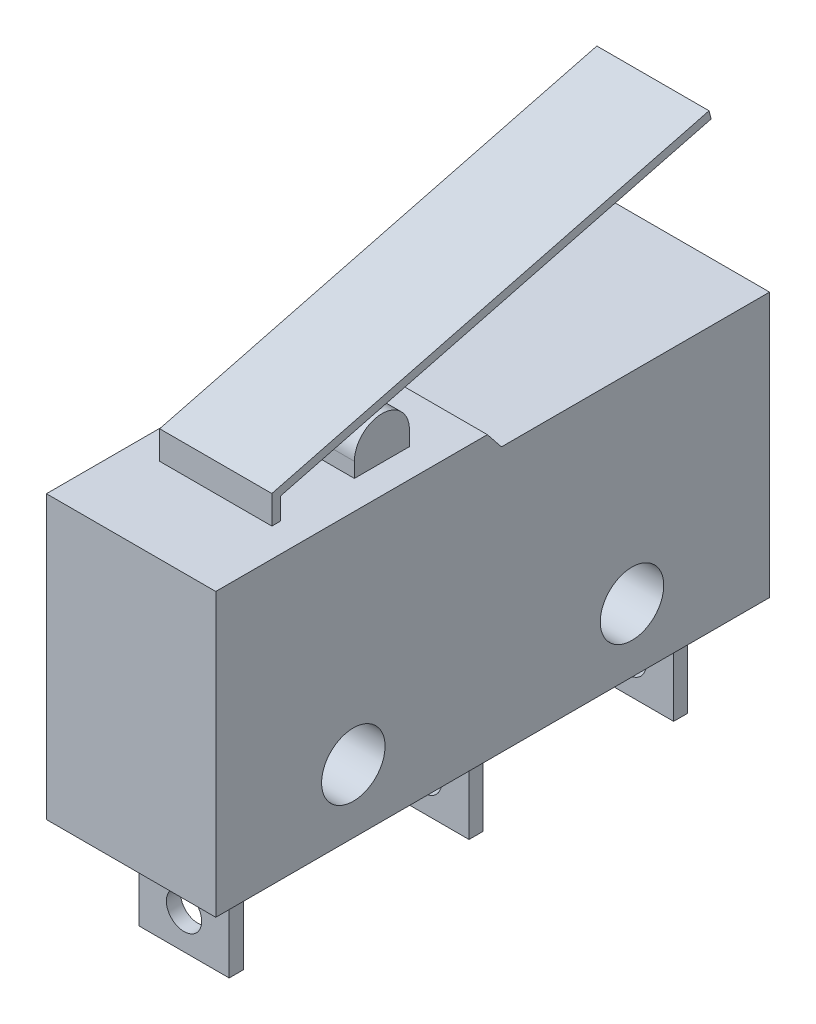
SolidWorks part; units mm, degrees
material "Nylon 101"
ref_plane "Front Plane" through (0, 0, 0) normal (0, 0, 1) x (1, 0, 0)
ref_plane "Top Plane" through (0, 0, 0) normal (0, 1, 0) x (1, 0, 0)
ref_plane "Right Plane" through (0, 0, 0) normal (1, 0, 0) x (0, 0, -1)
sketch "Sketch1" plane through (0, 0, 0) normal (1, 0, 0) x (0, 0, -1)
  line L0 (0, 0) -> (0, 10.16)
  line L1 (0, 10.16) -> (3.048, 10.16)
  line L2 (3.048, 10.16) -> (3.048, 11.176)
  line L3 (3.048, 11.176) -> (18.7878, 15.24)
  line L4 (3.3528, 10.16) -> (3.3528, 10.9399)
  line L5 (3.3528, 10.9399) -> (18.864, 14.9449)
  line L6 (18.7878, 15.24) -> (18.864, 14.9449)
  line L7 (3.3528, 10.16) -> (6.0198, 10.16)
  line L8 (6.0198, 10.16) -> (6.0198, 10.6934)
  line L9 (8.001, 10.6934) -> (8.001, 10.16)
  line L10 (8.001, 10.16) -> (9.779, 10.16)
  line L11 (10.287, 9.525) -> (19.939, 9.525)
  line L12 (9.779, 10.16) -> (10.287, 9.525)
  line L13 (0, 0) -> (1.905, 0)
  line L14 (19.939, 0) -> (19.939, 9.525)
  line L15 (1.905, 0) -> (1.905, -3.556)
  line L16 (1.905, -3.556) -> (2.413, -3.556)
  line L17 (2.413, -3.556) -> (2.413, 0)
  line L24 (2.413, 0) -> (10.541, 0)
  line L25 (11.049, -3.556) -> (11.049, 0)
  line L26 (10.541, 0) -> (10.541, -3.556)
  line L27 (10.541, -3.556) -> (11.049, -3.556)
  line L28 (18.415, -3.556) -> (18.415, 0)
  line L29 (17.907, 0) -> (17.907, -3.556)
  line L30 (17.907, -3.556) -> (18.415, -3.556)
  line L32 (18.415, 0) -> (19.939, 0)
  line L40 (11.049, 0) -> (17.907, 0)
  arc A0 (6.0198, 10.6934) -> (8.001, 10.6934) centre (7.0104, 10.6934) cw
  circle A1 centre (4.953, 2.286) radius 1.143
  circle A2 centre (14.986, 2.286) radius 1.143
  dimension "D5" = 0.9906
  dimension "D15" = 2.286
  dimension "D2" = 3.048
  dimension "D3" = 4.953
  dimension "D4" = 1.9812
  dimension "D6" = 0.5334
  dimension "D7" = 16.256
  dimension "D8" = 10.16
  dimension "D9" = 1.016
  dimension "D10" = 5.08
  dimension "D11" = 0.508
  dimension "D12" = 9.779
  dimension "D13" = 9.525
  dimension "D14" = 19.939
  dimension "D17" = 4.953
  dimension "D16" = 4.953
  dimension "D18" = 2.286
  dimension "D20" = 2.413
  dimension "D22" = 0.508
  dimension "D19" = 9.144
  dimension "D21" = 7.874
  dimension "D23" = 3.556
  dimension "D1" = 0.3048
extrude "MainBody" add sketch "Sketch1" along normal blind 6.096
sketch "Sketch2" plane through (0, 0, 0) normal (0, 0, 1) x (1, 0, 0)
  line L0 (0, 10.16) -> (1.0287, 10.16)
  line L1 (6.096, 10.16) -> (0, 10.16) construction
  line L2 (1.0287, 10.16) -> (1.0287, 15.24)
  line L3 (1.0287, 15.24) -> (5.0673, 15.24)
  line L4 (6.096, 15.24) -> (0, 15.24) construction
  line L5 (3.048, 15.24) -> (3.048, -4.8336) construction
  line L6 (0, 10.16) -> (0, 0)
  line L7 (0, 0) -> (1.4224, 0)
  line L8 (6.096, 0) -> (0, 0) construction
  line L9 (1.4224, 0) -> (1.4224, -3.556)
  line L10 (6.096, -3.556) -> (0, -3.556) construction
  line L11 (1.4224, -3.556) -> (4.6736, -3.556)
  line L12 (4.6736, 0) -> (4.6736, -3.556)
  line L13 (6.096, 0) -> (4.6736, 0)
  line L14 (6.096, 10.16) -> (6.096, 0)
  line L15 (5.0673, 10.16) -> (5.0673, 15.24)
  line L16 (6.096, 10.16) -> (5.0673, 10.16)
  circle A0 centre (3.048, -2.286) radius 0.635
  point P21 (3.048, -3.556)
  point P25 (3.048, 15.24)
  dimension "D3" = 1.27
  dimension "D1" = 4.0386
  dimension "D2" = 3.2512
  dimension "D4" = 1.27
extrude "SideTrim" cut sketch "Sketch2" against normal up to surface (19.939 mm away) flip side to cut up to face at (3.048, 4.7625, -19.939)
sketch "Sketch5" plane through (6.096, 0, 0) normal (1, 0, 0) x (0, 0, -1)
  line L0 (3.048, 0) -> (3.3655, -0.3302)
  line L1 (0, 0) -> (19.939, 0) construction
  line L2 (3.3655, -0.3302) -> (6.5405, -0.3302)
  line L3 (6.5405, -0.3302) -> (6.858, 0)
  line L5 (3.048, 0) -> (3.048, 2.286)
  line L6 (6.858, 2.286) -> (6.858, 0)
  line L7 (9.779, 10.16) -> (0, 10.16) construction
  line L8 (13.081, 0) -> (13.3985, -0.3302)
  line L9 (13.3985, -0.3302) -> (16.5735, -0.3302)
  line L10 (16.5735, -0.3302) -> (16.891, 0)
  line L11 (13.081, 0) -> (13.081, 2.286)
  line L12 (16.891, 2.286) -> (16.891, 0)
  arc A0 (3.048, 2.286) -> (6.858, 2.286) centre (4.953, 2.286) cw
  circle A3 centre (4.953, 2.286) radius 1.143 construction
  circle A4 centre (4.953, 2.286) radius 1.143
  arc A5 (13.081, 2.286) -> (16.891, 2.286) centre (14.986, 2.286) cw
  circle A6 centre (14.986, 2.286) radius 1.143
  circle A7 centre (14.986, 2.286) radius 1.143 construction
  point P12 (4.953, -0.3302)
  dimension "D1" = 3.81
  dimension "D2" = 3.175
  dimension "D3" = 10.4902
  dimension "D4" = 2
extrude "Nubs" [suppressed] add sketch "Sketch5" along normal blind 0.127 and the other way offset from surface 0.127
sketch "Sketch6" plane through (6.096, 0, 0) normal (1, 0, 0) x (0, 0, -1)
  line L0 (0.697, 0.4334) -> (3.621, 0.4334) construction
  line L1 (8.8752, 0.4334) -> (12.7148, 0.4334) construction
  line L2 (16.0882, 0.4334) -> (20.2338, 0.4334) construction
  line L4 (2.413, 0) -> (1.905, 0) construction
  line L5 (11.049, 0) -> (10.541, 0) construction
  line L6 (18.415, 0) -> (17.907, 0) construction
  text T0 "1" font "Century Gothic" height 1.778
  text T1 "2" font "Century Gothic" height 1.778
  text T2 "3" font "Century Gothic" height 1.778
  point P10 (2.159, 0)
  point P11 (2.159, 0.4334)
  point P12 (10.795, 0)
  point P13 (10.795, 0.4334)
  point P18 (18.161, 0)
  point P19 (18.161, 0.4334)
extrude "Boss-Extrude3" [suppressed] add sketch "Sketch6" along normal blind 0.127
fillet "Fillet1" [suppressed] radius 0.0254
equation "\"D6@Sketch1\"=0.06-\"D5@Sketch1\""
equation "\"D17@Sketch1\"=0.15+(\"D15@Sketch1\"/2)"
equation "\"D16@Sketch1\"=\"D17@Sketch1\""
